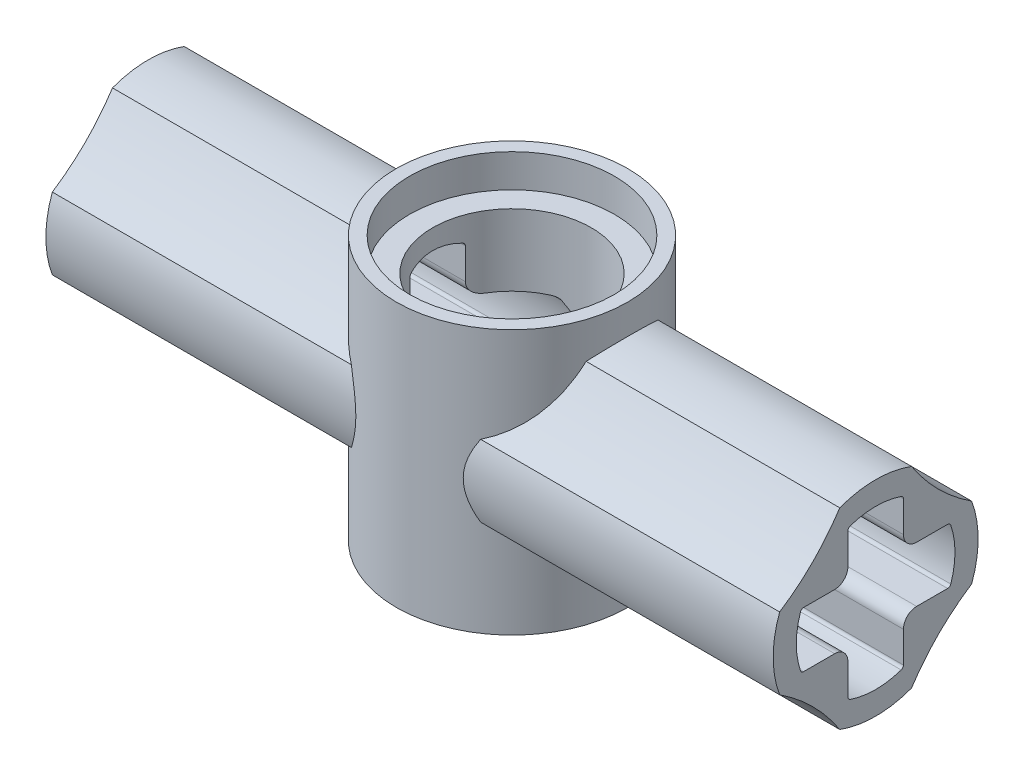
SolidWorks part; units mm, degrees
ref_plane "Front Plane" through (0, 0, 0) normal (0, 0, 1) x (1, 0, 0)
ref_plane "Top Plane" through (0, 0, 0) normal (0, 1, 0) x (1, 0, 0)
ref_plane "Right Plane" through (0, 0, 0) normal (1, 0, 0) x (0, 0, -1)
sketch "Sketch1" plane through (0, 0, 0) normal (1, 0, 0) x (0, 0, -1)
  line L0 (1.085, -1.085) -> (2.9039, -1.085)
  line L2 (-1.085, 2.9039) -> (-1.085, 1.085)
  line L4 (1.085, 2.9039) -> (1.085, 1.085)
  line L5 (-1.085, 2.9039) -> (1.085, -2.9039) construction
  line L6 (-1.085, -2.9039) -> (1.085, 2.9039) construction
  line L7 (-2.9039, 1.085) -> (-1.085, 1.085)
  line L9 (-2.9039, -1.085) -> (-1.085, -1.085)
  line L11 (-2.9039, 1.085) -> (2.9039, -1.085) construction
  line L12 (-2.9039, -1.085) -> (2.9039, 1.085) construction
  line L13 (1.085, -1.085) -> (1.085, -2.9039)
  line L14 (1.085, 1.085) -> (2.9039, 1.085)
  line L15 (-1.085, -1.085) -> (-1.085, -2.9039)
  arc A0 (1.085, 2.9039) -> (-1.085, 2.9039) centre (0, 0) ccw
  arc A1 (-2.9039, 1.085) -> (-2.9039, -1.085) centre (0, 0) ccw
  arc A2 (-1.085, -2.9039) -> (1.085, -2.9039) centre (0, 0) ccw
  arc A3 (2.9039, -1.085) -> (2.9039, 1.085) centre (0, 0) ccw
  dimension "D1" = 6.2
  dimension "D2" = 2.17
  dimension "D3" = 2.17
extrude "Boss-Extrude1" add sketch "Sketch1" against normal blind 22
fillet "Fillet1" radius 6.2 1 edges at (-11, 1.085, -1.085)
fillet "Fillet2" radius 6.2 1 edges at (-11, 1.085, 1.085)
fillet "Fillet3" radius 6.2 1 edges at (-11, -1.085, 1.085)
fillet "Fillet4" radius 6.2 1 edges at (-11, -1.085, -1.085)
sketch "Sketch3" plane through (0, 0, 0) normal (0, 1, 0) x (1, 0, 0)
  line L0 (0, 0) -> (-22, 0) construction
  line L1 (0, 0) -> (-11, 0) construction
  circle A0 centre (-11, 0) radius 3.5
  dimension "D2" = 7
  dimension "D1" = 22
extrude "Boss-Extrude2" add sketch "Sketch3" along normal mid plane 8
sketch "Sketch2" plane through (0, 0, 0) normal (1, 0, 0) x (0, 0, -1)
  line L0 (0.84, -0.84) -> (0.84, -2.2482)
  line L2 (-0.84, 2.2482) -> (-0.84, 0.84)
  line L4 (0.84, 2.2482) -> (0.84, 0.84)
  line L5 (-0.84, 2.2482) -> (0.84, -2.2482) construction
  line L6 (-0.84, -2.2482) -> (0.84, 2.2482) construction
  line L7 (-2.2482, 0.84) -> (-0.84, 0.84)
  line L9 (-2.2482, -0.84) -> (-0.84, -0.84)
  line L11 (-2.2482, 0.84) -> (2.2482, -0.84) construction
  line L12 (-2.2482, -0.84) -> (2.2482, 0.84) construction
  line L13 (0.84, 0.84) -> (2.2482, 0.84)
  line L14 (-0.84, -0.84) -> (-0.84, -2.2482)
  line L15 (0.84, -0.84) -> (2.2482, -0.84)
  arc A0 (0.84, 2.2482) -> (-0.84, 2.2482) centre (0, 0) ccw
  arc A1 (-2.2482, 0.84) -> (-2.2482, -0.84) centre (0, 0) ccw
  arc A2 (-0.84, -2.2482) -> (0.84, -2.2482) centre (0, 0) ccw
  arc A3 (2.2482, -0.84) -> (2.2482, 0.84) centre (0, 0) ccw
  dimension "D1" = 4.8
  dimension "D2" = 1.68
  dimension "D3" = 1.68
extrude "Cut-Extrude1" cut sketch "Sketch2" against normal through all
fillet "Fillet5" radius 0.4 1 edges at (-11, 0.84, -0.84)
fillet "Fillet6" radius 0.4 1 edges at (-11, 0.84, 0.84)
fillet "Fillet7" radius 0.4 1 edges at (-11, -0.84, 0.84)
fillet "Fillet8" radius 0.4 1 edges at (-11, -0.84, -0.84)
fillet "Fillet9" radius 0.1 1 edges at (-11, -2.2482, 0.84)
fillet "Fillet10" radius 0.1 1 edges at (-11, -2.2482, -0.84)
fillet "Fillet11" radius 0.1 1 edges at (-11, 0.84, 2.2482)
fillet "Fillet12" radius 0.1 1 edges at (-11, -0.84, 2.2482)
fillet "Fillet13" radius 0.1 1 edges at (-11, 2.2482, 0.84)
fillet "Fillet14" radius 0.1 1 edges at (-11, 2.2482, -0.84)
fillet "Fillet15" radius 0.1 1 edges at (-11, 0.84, -2.2482)
fillet "Fillet16" radius 0.1 1 edges at (-11, -0.84, -2.2482)
sketch "Sketch4" plane through (0, 4, 0) normal (0, 1, 0) x (1, 0, 0)
  line L0 (0, 0) -> (-11, 0) construction
  circle A0 centre (-11, 0) radius 2.4
  dimension "D1" = 4.8
extrude "Cut-Extrude2" cut sketch "Sketch4" against normal through all
sketch "Sketch5" plane through (0, 4, 0) normal (0, 1, 0) x (1, 0, 0)
  circle A0 centre (-11, 0) radius 3.1
  dimension "D1" = 6.2
extrude "Cut-Extrude3" cut sketch "Sketch5" against normal blind 1
mirror "Mirror1" about plane through (0, 0, 0) normal (0, 1, 0) of "Cut-Extrude3"
